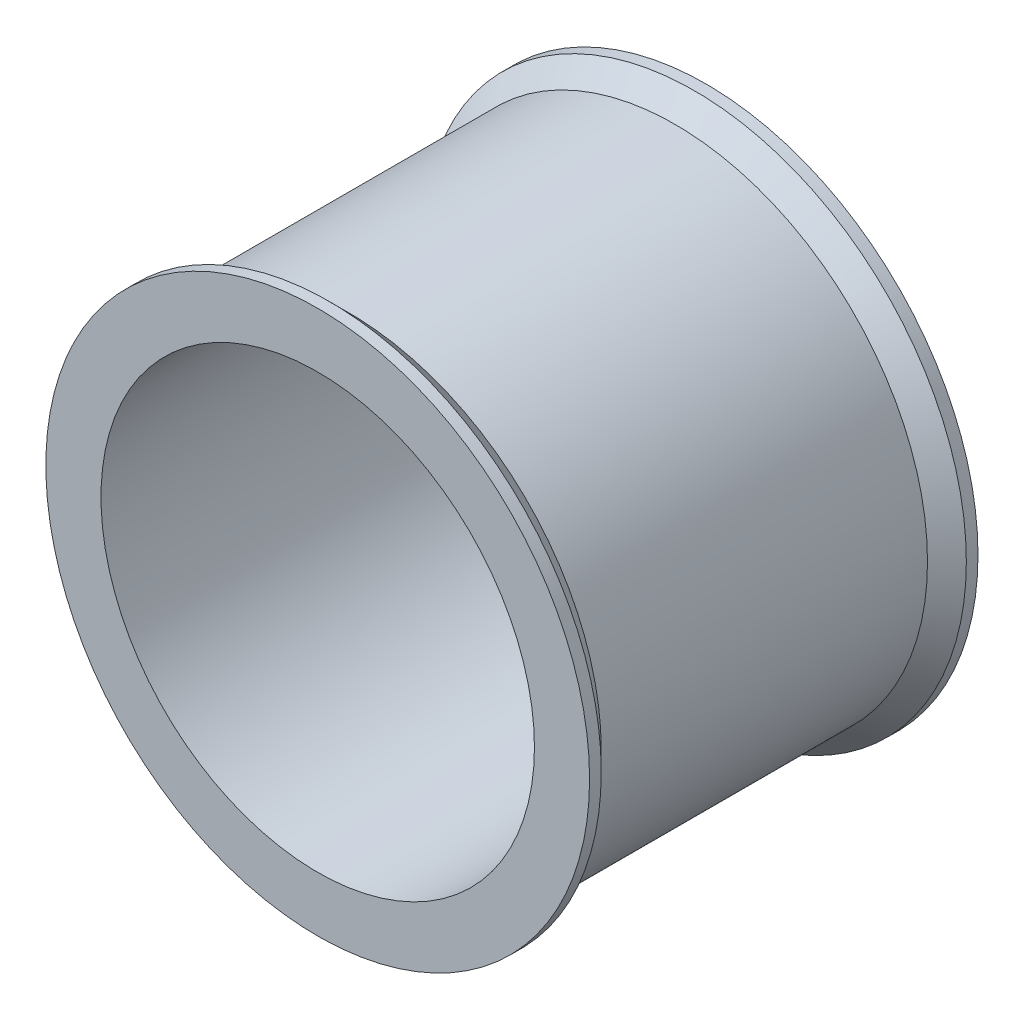
SolidWorks part; units mm, degrees
ref_plane "Front Plane" through (0, 0, 0) normal (0, 0, 1) x (1, 0, 0)
ref_plane "Top Plane" through (0, 0, 0) normal (0, 1, 0) x (1, 0, 0)
ref_plane "Right Plane" through (0, 0, 0) normal (1, 0, 0) x (0, 0, -1)
sketch "Sketch1" plane through (0, 0, 0) normal (0, 0, 1) x (1, 0, 0)
  circle A0 centre (0, 0) radius 5.58
  circle A1 centre (0, 0) radius 6.5
  dimension "D1" = 11.16
  dimension "D2" = 13
extrude "Boss-Extrude1" add sketch "Sketch1" along normal mid plane 10
sketch "Sketch2" plane through (0, 0, -5) normal (0, 0, 1) x (1, 0, 0)
  circle A1 centre (0, 0) radius 6.5 construction
  circle A2 centre (0, 0) radius 7
  circle A3 centre (0, 0) radius 7
  circle A4 centre (0, 0) radius 6.5
  dimension "D1" = 0.5
extrude "Boss-Extrude2" add sketch "Sketch2" along normal blind 1
mirror "Mirror1" about plane through (0, 0, 0) normal (0, 0, 1) of "Boss-Extrude2"
chamfer "Chamfer1" distance 0.7 angle 45 2 edges at (7, 0, 4) (7, 0, -4)
